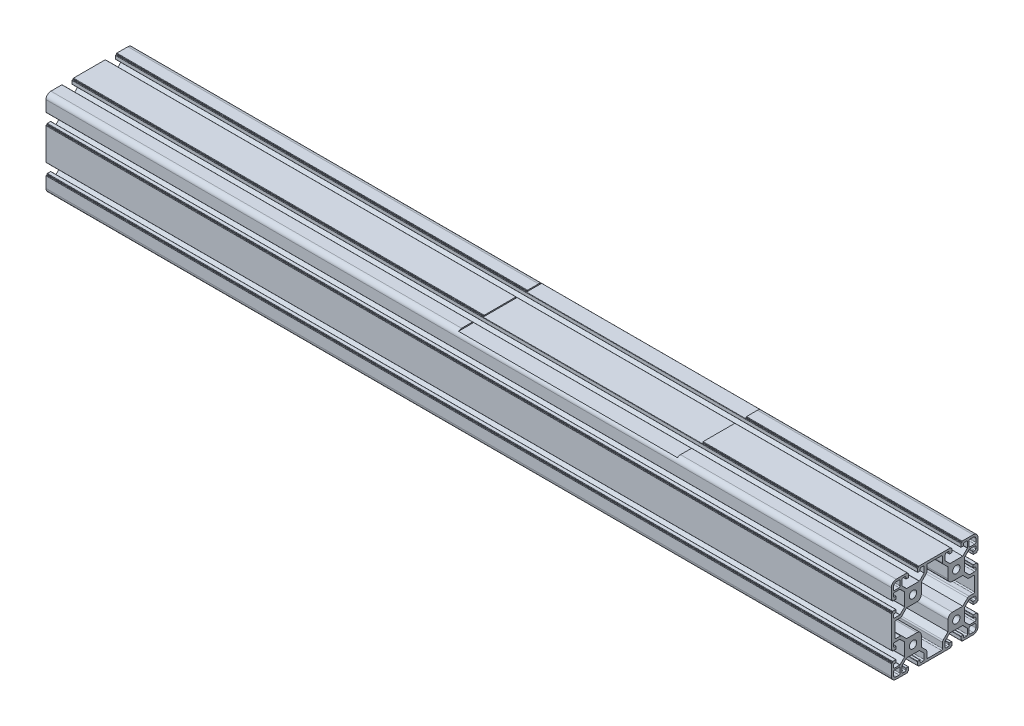
SolidWorks part; units mm, degrees
ref_plane "前视基准面" through (0, 0, 0) normal (0, 0, 1) x (1, 0, 0)
ref_plane "上视基准面" through (0, 0, 0) normal (0, 1, 0) x (1, 0, 0)
ref_plane "右视基准面" through (0, 0, 0) normal (1, 0, 0) x (0, 0, -1)
sketch "草图1" plane through (0, 0, 0) normal (0, 0, 1) x (1, 0, 0)
  line L0 (0, 0) -> (780, 0)
  dimension "D1" = 780
other "铝型材（gb t5237-2004） 8080(1)" corner treatment miter
ref_plane "基准面1" through (0, 0, 0) normal (1, 0, 0) x (0, 1, 0)
sketch "草图19" plane through (0, 0, 0) normal (1, 0, 0) x (0, 1, 0)
  line L2 (-25.808, -27.7) -> (-14.192, -27.7)
  line L3 (-14.9, 39.7) -> (-14.9, 39.2)
  line L4 (-10.75, -38) -> (-12.4, -38)
  line L5 (-15.9, -35.8) -> (-15.9, -38.7)
  line L6 (-15.6, -39) -> (-15.1, -39)
  line L7 (10.75, 38) -> (12.4, 38)
  line L8 (14.9, -39.7) -> (14.9, -39.2)
  line L9 (25.808, 27.7) -> (14.192, 27.7)
  line L10 (30.1621, 31.9299) -> (26.0201, 27.7879)
  line L11 (15.6, -35.5) -> (13.7, -35.5)
  line L12 (27.6, 38) -> (29.25, 38)
  line L13 (26.6, 35.8) -> (26.6, 37)
  line L14 (9.75, -37) -> (9.75, -32.142)
  line L15 (24.1, 38.7) -> (24.1, 35.8)
  line L16 (9.8379, -31.9299) -> (13.9799, -27.7879)
  line L17 (24.9, 39) -> (24.4, 39)
  line L18 (26.0201, -27.7879) -> (30.1621, -31.9299)
  line L19 (30.25, -32.142) -> (30.25, -37)
  line L20 (31.8107, 7.25) -> (36.8, 7.25)
  line L21 (-37.8, -6.25) -> (-37.8, 6.25)
  line L25 (-35.5, 13.7) -> (-35.5, 15.6)
  line L26 (-35.8, 15.9) -> (-38.7, 15.9)
  line L27 (-37, 13.4) -> (-35.8, 13.4)
  line L28 (-39, 15.6) -> (-39, 15.1)
  line L29 (-38, 10.75) -> (-38, 12.4)
  line L30 (-39.2, 14.9) -> (-39.7, 14.9)
  line L31 (-32.0178, 9.75) -> (-37, 9.75)
  line L32 (-27.7879, 13.9799) -> (-32.0178, 9.75)
  line L33 (-40, 14.6) -> (-40, -14.6)
  line L34 (-27.7, 25.808) -> (-27.7, 14.192)
  line L35 (-39.7, -14.9) -> (-39.2, -14.9)
  line L36 (-31.9299, 30.1621) -> (-27.7879, 26.0201)
  line L37 (-39, -15.1) -> (-39, -15.6)
  line L38 (-37, 30.25) -> (-32.142, 30.25)
  line L39 (-38.7, -15.9) -> (-35.8, -15.9)
  line L40 (-38, 27.6) -> (-38, 29.25)
  line L41 (-35.5, -15.6) -> (-35.5, -13.7)
  line L42 (-35.8, 26.6) -> (-37, 26.6)
  line L43 (-35.8, -13.4) -> (-37, -13.4)
  line L44 (-35.5, 24.4) -> (-35.5, 26.3)
  line L45 (-38, -12.4) -> (-38, -10.75)
  line L46 (-38.7, 24.1) -> (-35.8, 24.1)
  line L47 (-37, -9.75) -> (-32.0178, -9.75)
  line L48 (-32.0178, -9.75) -> (-27.7879, -13.9799)
  line L49 (-39, 24.9) -> (-39, 24.4)
  line L50 (-27.7, -14.192) -> (-27.7, -25.808)
  line L51 (-39.7, 25.1) -> (-39.2, 25.1)
  line L52 (-27.7879, -26.0201) -> (-31.9299, -30.1621)
  line L53 (-40, 35.5) -> (-40, 25.4)
  line L54 (-32.142, -30.25) -> (-37, -30.25)
  line L55 (-25.4, 40) -> (-35.5, 40)
  line L56 (-38, -29.25) -> (-38, -27.6)
  line L57 (-25.1, 39.2) -> (-25.1, 39.7)
  line L58 (-37, -26.6) -> (-35.8, -26.6)
  line L59 (-24.4, 39) -> (-24.9, 39)
  line L60 (-35.5, -26.3) -> (-35.5, -24.4)
  line L61 (-24.1, 35.8) -> (-24.1, 38.7)
  line L62 (-35.8, -24.1) -> (-38.7, -24.1)
  line L63 (-26.3, 35.5) -> (-24.4, 35.5)
  line L64 (-39, -24.4) -> (-39, -24.9)
  line L65 (-26.6, 37) -> (-26.6, 35.8)
  line L66 (-39.2, -25.1) -> (-39.7, -25.1)
  line L67 (-29.25, 38) -> (-27.6, 38)
  line L68 (-40, -25.4) -> (-40, -35.5)
  line L69 (-30.25, 32.142) -> (-30.25, 37)
  line L70 (-35.5, -40) -> (-25.4, -40)
  line L71 (-26.0201, 27.7879) -> (-30.1621, 31.9299)
  line L72 (-25.1, -39.7) -> (-25.1, -39.2)
  line L73 (-14.192, 27.7) -> (-25.808, 27.7)
  line L74 (-24.9, -39) -> (-24.4, -39)
  line L75 (-9.8379, 31.9299) -> (-13.9799, 27.7879)
  line L76 (-24.1, -38.7) -> (-24.1, -35.8)
  line L77 (-9.75, 37) -> (-9.75, 32.142)
  line L78 (-24.4, -35.5) -> (-26.3, -35.5)
  line L79 (-12.4, 38) -> (-10.75, 38)
  line L80 (-26.6, -35.8) -> (-26.6, -37)
  line L81 (-13.4, 35.8) -> (-13.4, 37)
  line L82 (-27.6, -38) -> (-29.25, -38)
  line L83 (-15.6, 35.5) -> (-13.7, 35.5)
  line L84 (-30.25, -37) -> (-30.25, -32.142)
  line L85 (-15.9, 38.7) -> (-15.9, 35.8)
  line L86 (-30.1621, -31.9299) -> (-26.0201, -27.7879)
  line L87 (-15.1, 39) -> (-15.6, 39)
  line L88 (-13.9799, -27.7879) -> (-9.8379, -31.9299)
  line L89 (14.6, 40) -> (-14.6, 40)
  line L90 (-9.75, -32.142) -> (-9.75, -37)
  line L91 (14.9, 39.2) -> (14.9, 39.7)
  line L92 (15.6, 39) -> (15.1, 39)
  line L93 (-13.4, -37) -> (-13.4, -35.8)
  line L94 (15.9, 35.8) -> (15.9, 38.7)
  line L95 (-13.7, -35.5) -> (-15.6, -35.5)
  line L96 (13.7, 35.5) -> (15.6, 35.5)
  line L97 (13.4, 37) -> (13.4, 35.8)
  line L98 (-14.9, -39.2) -> (-14.9, -39.7)
  line L99 (9.75, 32.142) -> (9.75, 37)
  line L100 (-14.6, -40) -> (14.6, -40)
  line L101 (13.9799, 27.7879) -> (9.8379, 31.9299)
  line L102 (15.1, -39) -> (15.6, -39)
  line L103 (15.9, -38.7) -> (15.9, -35.8)
  line L104 (30.25, 37) -> (30.25, 32.142)
  line L105 (13.4, -35.8) -> (13.4, -37)
  line L106 (12.4, -38) -> (10.75, -38)
  line L107 (24.4, 35.5) -> (26.3, 35.5)
  line L108 (14.192, -27.7) -> (25.808, -27.7)
  line L109 (25.1, 39.7) -> (25.1, 39.2)
  line L110 (35.5, 40) -> (25.4, 40)
  line L111 (40, 25.4) -> (40, 35.5)
  line L112 (29.25, -38) -> (27.6, -38)
  line L113 (39.2, 25.1) -> (39.7, 25.1)
  line L114 (26.6, -37) -> (26.6, -35.8)
  line L115 (39, 24.4) -> (39, 24.9)
  line L116 (26.3, -35.5) -> (24.4, -35.5)
  line L117 (35.8, 24.1) -> (38.7, 24.1)
  line L118 (24.1, -35.8) -> (24.1, -38.7)
  line L119 (35.5, 26.3) -> (35.5, 24.4)
  line L120 (24.4, -39) -> (24.9, -39)
  line L121 (37, 26.6) -> (35.8, 26.6)
  line L122 (25.1, -39.2) -> (25.1, -39.7)
  line L123 (38, 29.25) -> (38, 27.6)
  line L124 (25.4, -40) -> (35.5, -40)
  line L125 (32.142, 30.25) -> (37, 30.25)
  line L126 (40, -35.5) -> (40, -25.4)
  line L127 (27.7879, 26.0201) -> (31.9299, 30.1621)
  line L128 (39.7, -25.1) -> (39.2, -25.1)
  line L129 (27.7, 14.192) -> (27.7, 25.808)
  line L130 (39, -24.9) -> (39, -24.4)
  line L131 (32.0178, 9.75) -> (27.7879, 13.9799)
  line L132 (37, 9.75) -> (32.0178, 9.75)
  line L133 (38.7, -24.1) -> (35.8, -24.1)
  line L134 (38, 12.4) -> (38, 10.75)
  line L135 (35.5, -24.4) -> (35.5, -26.3)
  line L136 (35.8, 13.4) -> (37, 13.4)
  line L137 (35.8, -26.6) -> (37, -26.6)
  line L138 (35.5, 15.6) -> (35.5, 13.7)
  line L139 (38, -27.6) -> (38, -29.25)
  line L140 (38.7, 15.9) -> (35.8, 15.9)
  line L141 (37, -30.25) -> (32.142, -30.25)
  line L142 (39, 15.1) -> (39, 15.6)
  line L143 (31.9299, -30.1621) -> (27.7, -25.9322)
  line L144 (27.7, -25.9322) -> (27.7, -14.0678)
  line L145 (39.7, 14.9) -> (39.2, 14.9)
  line L146 (27.7, -14.0678) -> (32.0178, -9.75)
  line L147 (32.0178, -9.75) -> (37, -9.75)
  line L148 (40, -14.6) -> (40, 14.6)
  line L149 (38, -10.75) -> (38, -12.4)
  line L150 (39.2, -14.9) -> (39.7, -14.9)
  line L151 (37, -13.4) -> (35.8, -13.4)
  line L152 (39, -15.6) -> (39, -15.1)
  line L153 (35.5, -13.7) -> (35.5, -15.6)
  line L154 (35.8, -15.9) -> (38.7, -15.9)
  line L155 (-6.25, 36.8) -> (6.25, 36.8)
  line L156 (7.25, 35.8) -> (7.25, 31.8107)
  line L157 (-7.25, 31.8107) -> (-7.25, 35.8)
  line L158 (7.8358, 30.3964) -> (12.3, 25.9322)
  line L159 (-12.3, 25.9322) -> (-7.8358, 30.3964)
  line L160 (12.3, 25.9322) -> (12.3, 16.3)
  line L161 (-12.3, 16.3) -> (-12.3, 25.9322)
  line L162 (16.3, 12.3) -> (25.9322, 12.3)
  line L163 (-25.9322, 12.3) -> (-16.3, 12.3)
  line L164 (25.9322, 12.3) -> (30.3964, 7.8358)
  line L165 (-30.3964, 7.8358) -> (-25.9322, 12.3)
  line L166 (-36.8, 7.25) -> (-31.8107, 7.25)
  line L167 (37.8, 6.25) -> (37.8, -6.25)
  line L168 (36.8, -7.25) -> (31.8107, -7.25)
  line L169 (-31.8107, -7.25) -> (-36.8, -7.25)
  line L170 (30.3964, -7.8358) -> (25.9322, -12.3)
  line L171 (-25.9322, -12.3) -> (-30.3964, -7.8358)
  line L172 (25.9322, -12.3) -> (16.3, -12.3)
  line L173 (-16.3, -12.3) -> (-25.9322, -12.3)
  line L174 (12.3, -16.3) -> (12.3, -25.9322)
  line L175 (-12.3, -25.9322) -> (-12.3, -16.3)
  line L176 (12.3, -25.9322) -> (7.8358, -30.3964)
  line L177 (-7.8358, -30.3964) -> (-12.3, -25.9322)
  line L178 (7.25, -31.8107) -> (7.25, -35.8)
  line L179 (-7.25, -35.8) -> (-7.25, -31.8107)
  line L180 (6.25, -36.8) -> (-6.25, -36.8)
  line L181 (38, 35.5) -> (38, 32.75)
  line L182 (32.75, 38) -> (35.5, 38)
  line L183 (37, 31.75) -> (32.75, 31.75)
  line L184 (31.75, 32.75) -> (31.75, 37)
  line L185 (-35.5, 38) -> (-32.75, 38)
  line L186 (-38, 32.75) -> (-38, 35.5)
  line L187 (-31.75, 37) -> (-31.75, 32.75)
  line L188 (-32.75, 31.75) -> (-37, 31.75)
  line L189 (-38, -35.5) -> (-38, -32.75)
  line L190 (-32.75, -38) -> (-35.5, -38)
  line L191 (-37, -31.75) -> (-32.75, -31.75)
  line L192 (-31.75, -32.75) -> (-31.75, -37)
  line L193 (35.5, -38) -> (32.75, -38)
  line L194 (38, -32.75) -> (38, -35.5)
  line L195 (31.75, -37) -> (31.75, -32.75)
  line L196 (32.75, -31.75) -> (37, -31.75)
  arc A0 (-9.75, -32.142) -> (-9.8379, -31.9299) centre (-10.05, -32.142) ccw
  arc A1 (14.9, 39.7) -> (14.6, 40) centre (14.6, 39.7) ccw
  arc A2 (-15.6, -35.5) -> (-15.9, -35.8) centre (-15.6, -35.8) ccw
  arc A3 (13.4, 35.8) -> (13.7, 35.5) centre (13.7, 35.8) ccw
  arc A4 (-14.9, -39.2) -> (-15.1, -39) centre (-15.1, -39.2) ccw
  arc A5 (9.75, 32.142) -> (9.8379, 31.9299) centre (10.05, 32.142) ccw
  arc A6 (15.6, -39) -> (15.9, -38.7) centre (15.6, -38.7) ccw
  arc A7 (30.1621, 31.9299) -> (30.25, 32.142) centre (29.95, 32.142) ccw
  arc A8 (30.25, 37) -> (29.25, 38) centre (29.25, 37) ccw
  arc A9 (12.4, -38) -> (13.4, -37) centre (12.4, -37) ccw
  arc A10 (26.3, 35.5) -> (26.6, 35.8) centre (26.3, 35.8) ccw
  arc A11 (24.1, 35.8) -> (24.4, 35.5) centre (24.4, 35.8) ccw
  arc A12 (14.192, -27.7) -> (13.9799, -27.7879) centre (14.192, -28) ccw
  arc A13 (24.9, 39) -> (25.1, 39.2) centre (24.9, 39.2) ccw
  arc A14 (26.0201, -27.7879) -> (25.808, -27.7) centre (25.808, -28) ccw
  arc A15 (25.4, 40) -> (25.1, 39.7) centre (25.4, 39.7) ccw
  arc A16 (-31.8107, 7.25) -> (-30.3964, 7.8358) centre (-31.8107, 9.25) ccw
  arc A17 (36.8, -7.25) -> (37.8, -6.25) centre (36.8, -6.25) ccw
  arc A18 (-35.5, 15.6) -> (-35.8, 15.9) centre (-35.8, 15.6) ccw
  arc A19 (-35.8, 13.4) -> (-35.5, 13.7) centre (-35.8, 13.7) ccw
  arc A20 (-38.7, 15.9) -> (-39, 15.6) centre (-38.7, 15.6) ccw
  arc A21 (-37, 13.4) -> (-38, 12.4) centre (-37, 12.4) ccw
  arc A22 (-39.2, 14.9) -> (-39, 15.1) centre (-39.2, 15.1) ccw
  arc A23 (-38, 10.75) -> (-37, 9.75) centre (-37, 10.75) ccw
  arc A24 (-39.7, 14.9) -> (-40, 14.6) centre (-39.7, 14.6) ccw
  arc A25 (-27.7879, 13.9799) -> (-27.7, 14.192) centre (-28, 14.192) ccw
  arc A26 (-40, -14.6) -> (-39.7, -14.9) centre (-39.7, -14.6) ccw
  arc A27 (-27.7, 25.808) -> (-27.7879, 26.0201) centre (-28, 25.808) ccw
  arc A28 (-39, -15.1) -> (-39.2, -14.9) centre (-39.2, -15.1) ccw
  arc A29 (-31.9299, 30.1621) -> (-32.142, 30.25) centre (-32.142, 29.95) ccw
  arc A30 (-39, -15.6) -> (-38.7, -15.9) centre (-38.7, -15.6) ccw
  arc A31 (-37, 30.25) -> (-38, 29.25) centre (-37, 29.25) ccw
  arc A32 (-35.8, -15.9) -> (-35.5, -15.6) centre (-35.8, -15.6) ccw
  arc A33 (-38, 27.6) -> (-37, 26.6) centre (-37, 27.6) ccw
  arc A34 (-35.5, -13.7) -> (-35.8, -13.4) centre (-35.8, -13.7) ccw
  arc A35 (-35.5, 26.3) -> (-35.8, 26.6) centre (-35.8, 26.3) ccw
  arc A36 (-38, -12.4) -> (-37, -13.4) centre (-37, -12.4) ccw
  arc A37 (-35.8, 24.1) -> (-35.5, 24.4) centre (-35.8, 24.4) ccw
  arc A38 (-37, -9.75) -> (-38, -10.75) centre (-37, -10.75) ccw
  arc A39 (-39, 24.4) -> (-38.7, 24.1) centre (-38.7, 24.4) ccw
  arc A40 (-27.7, -14.192) -> (-27.7879, -13.9799) centre (-28, -14.192) ccw
  arc A41 (-39, 24.9) -> (-39.2, 25.1) centre (-39.2, 24.9) ccw
  arc A42 (-27.7879, -26.0201) -> (-27.7, -25.808) centre (-28, -25.808) ccw
  arc A43 (-40, 25.4) -> (-39.7, 25.1) centre (-39.7, 25.4) ccw
  arc A44 (-32.142, -30.25) -> (-31.9299, -30.1621) centre (-32.142, -29.95) ccw
  arc A45 (-35.5, 40) -> (-40, 35.5) centre (-35.5, 35.5) ccw
  arc A46 (-38, -29.25) -> (-37, -30.25) centre (-37, -29.25) ccw
  arc A47 (-25.1, 39.7) -> (-25.4, 40) centre (-25.4, 39.7) ccw
  arc A48 (-37, -26.6) -> (-38, -27.6) centre (-37, -27.6) ccw
  arc A49 (-25.1, 39.2) -> (-24.9, 39) centre (-24.9, 39.2) ccw
  arc A50 (-35.8, -26.6) -> (-35.5, -26.3) centre (-35.8, -26.3) ccw
  arc A51 (-24.1, 38.7) -> (-24.4, 39) centre (-24.4, 38.7) ccw
  arc A52 (-35.5, -24.4) -> (-35.8, -24.1) centre (-35.8, -24.4) ccw
  arc A53 (-24.4, 35.5) -> (-24.1, 35.8) centre (-24.4, 35.8) ccw
  arc A54 (-38.7, -24.1) -> (-39, -24.4) centre (-38.7, -24.4) ccw
  arc A55 (-26.6, 35.8) -> (-26.3, 35.5) centre (-26.3, 35.8) ccw
  arc A56 (-39.2, -25.1) -> (-39, -24.9) centre (-39.2, -24.9) ccw
  arc A57 (-26.6, 37) -> (-27.6, 38) centre (-27.6, 37) ccw
  arc A58 (-39.7, -25.1) -> (-40, -25.4) centre (-39.7, -25.4) ccw
  arc A59 (-29.25, 38) -> (-30.25, 37) centre (-29.25, 37) ccw
  arc A60 (-40, -35.5) -> (-35.5, -40) centre (-35.5, -35.5) ccw
  arc A61 (-30.25, 32.142) -> (-30.1621, 31.9299) centre (-29.95, 32.142) ccw
  arc A62 (-25.4, -40) -> (-25.1, -39.7) centre (-25.4, -39.7) ccw
  arc A63 (-26.0201, 27.7879) -> (-25.808, 27.7) centre (-25.808, 28) ccw
  arc A64 (-24.9, -39) -> (-25.1, -39.2) centre (-24.9, -39.2) ccw
  arc A65 (-14.192, 27.7) -> (-13.9799, 27.7879) centre (-14.192, 28) ccw
  arc A66 (-24.4, -39) -> (-24.1, -38.7) centre (-24.4, -38.7) ccw
  arc A67 (-9.8379, 31.9299) -> (-9.75, 32.142) centre (-10.05, 32.142) ccw
  arc A68 (-24.1, -35.8) -> (-24.4, -35.5) centre (-24.4, -35.8) ccw
  arc A69 (-9.75, 37) -> (-10.75, 38) centre (-10.75, 37) ccw
  arc A70 (-26.3, -35.5) -> (-26.6, -35.8) centre (-26.3, -35.8) ccw
  arc A71 (-12.4, 38) -> (-13.4, 37) centre (-12.4, 37) ccw
  arc A72 (-27.6, -38) -> (-26.6, -37) centre (-27.6, -37) ccw
  arc A73 (-13.7, 35.5) -> (-13.4, 35.8) centre (-13.7, 35.8) ccw
  arc A74 (-30.25, -37) -> (-29.25, -38) centre (-29.25, -37) ccw
  arc A75 (-15.9, 35.8) -> (-15.6, 35.5) centre (-15.6, 35.8) ccw
  arc A76 (-30.1621, -31.9299) -> (-30.25, -32.142) centre (-29.95, -32.142) ccw
  arc A77 (-15.6, 39) -> (-15.9, 38.7) centre (-15.6, 38.7) ccw
  arc A78 (-25.808, -27.7) -> (-26.0201, -27.7879) centre (-25.808, -28) ccw
  arc A79 (-15.1, 39) -> (-14.9, 39.2) centre (-15.1, 39.2) ccw
  arc A80 (-13.9799, -27.7879) -> (-14.192, -27.7) centre (-14.192, -28) ccw
  arc A81 (-14.6, 40) -> (-14.9, 39.7) centre (-14.6, 39.7) ccw
  arc A82 (-10.75, -38) -> (-9.75, -37) centre (-10.75, -37) ccw
  arc A83 (14.9, 39.2) -> (15.1, 39) centre (15.1, 39.2) ccw
  arc A84 (-13.4, -37) -> (-12.4, -38) centre (-12.4, -37) ccw
  arc A85 (15.9, 38.7) -> (15.6, 39) centre (15.6, 38.7) ccw
  arc A86 (-13.4, -35.8) -> (-13.7, -35.5) centre (-13.7, -35.8) ccw
  arc A87 (15.6, 35.5) -> (15.9, 35.8) centre (15.6, 35.8) ccw
  arc A88 (-15.9, -38.7) -> (-15.6, -39) centre (-15.6, -38.7) ccw
  arc A89 (13.4, 37) -> (12.4, 38) centre (12.4, 37) ccw
  arc A90 (10.75, 38) -> (9.75, 37) centre (10.75, 37) ccw
  arc A91 (-14.9, -39.7) -> (-14.6, -40) centre (-14.6, -39.7) ccw
  arc A92 (14.6, -40) -> (14.9, -39.7) centre (14.6, -39.7) ccw
  arc A93 (13.9799, 27.7879) -> (14.192, 27.7) centre (14.192, 28) ccw
  arc A94 (15.1, -39) -> (14.9, -39.2) centre (15.1, -39.2) ccw
  arc A95 (25.808, 27.7) -> (26.0201, 27.7879) centre (25.808, 28) ccw
  arc A96 (15.9, -35.8) -> (15.6, -35.5) centre (15.6, -35.8) ccw
  arc A97 (13.7, -35.5) -> (13.4, -35.8) centre (13.7, -35.8) ccw
  arc A98 (27.6, 38) -> (26.6, 37) centre (27.6, 37) ccw
  arc A99 (9.75, -37) -> (10.75, -38) centre (10.75, -37) ccw
  arc A100 (9.8379, -31.9299) -> (9.75, -32.142) centre (10.05, -32.142) ccw
  arc A101 (24.4, 39) -> (24.1, 38.7) centre (24.4, 38.7) ccw
  arc A102 (30.25, -32.142) -> (30.1621, -31.9299) centre (29.95, -32.142) ccw
  arc A103 (40, 35.5) -> (35.5, 40) centre (35.5, 35.5) ccw
  arc A104 (29.25, -38) -> (30.25, -37) centre (29.25, -37) ccw
  arc A105 (39.7, 25.1) -> (40, 25.4) centre (39.7, 25.4) ccw
  arc A106 (26.6, -37) -> (27.6, -38) centre (27.6, -37) ccw
  arc A107 (39.2, 25.1) -> (39, 24.9) centre (39.2, 24.9) ccw
  arc A108 (26.6, -35.8) -> (26.3, -35.5) centre (26.3, -35.8) ccw
  arc A109 (38.7, 24.1) -> (39, 24.4) centre (38.7, 24.4) ccw
  arc A110 (24.4, -35.5) -> (24.1, -35.8) centre (24.4, -35.8) ccw
  arc A111 (35.5, 24.4) -> (35.8, 24.1) centre (35.8, 24.4) ccw
  arc A112 (24.1, -38.7) -> (24.4, -39) centre (24.4, -38.7) ccw
  arc A113 (35.8, 26.6) -> (35.5, 26.3) centre (35.8, 26.3) ccw
  arc A114 (25.1, -39.2) -> (24.9, -39) centre (24.9, -39.2) ccw
  arc A115 (37, 26.6) -> (38, 27.6) centre (37, 27.6) ccw
  arc A116 (25.1, -39.7) -> (25.4, -40) centre (25.4, -39.7) ccw
  arc A117 (38, 29.25) -> (37, 30.25) centre (37, 29.25) ccw
  arc A118 (35.5, -40) -> (40, -35.5) centre (35.5, -35.5) ccw
  arc A119 (32.142, 30.25) -> (31.9299, 30.1621) centre (32.142, 29.95) ccw
  arc A120 (40, -25.4) -> (39.7, -25.1) centre (39.7, -25.4) ccw
  arc A121 (27.7879, 26.0201) -> (27.7, 25.808) centre (28, 25.808) ccw
  arc A122 (39, -24.9) -> (39.2, -25.1) centre (39.2, -24.9) ccw
  arc A123 (27.7, 14.192) -> (27.7879, 13.9799) centre (28, 14.192) ccw
  arc A124 (39, -24.4) -> (38.7, -24.1) centre (38.7, -24.4) ccw
  arc A125 (37, 9.75) -> (38, 10.75) centre (37, 10.75) ccw
  arc A126 (35.8, -24.1) -> (35.5, -24.4) centre (35.8, -24.4) ccw
  arc A127 (38, 12.4) -> (37, 13.4) centre (37, 12.4) ccw
  arc A128 (35.5, -26.3) -> (35.8, -26.6) centre (35.8, -26.3) ccw
  arc A129 (35.5, 13.7) -> (35.8, 13.4) centre (35.8, 13.7) ccw
  arc A130 (38, -27.6) -> (37, -26.6) centre (37, -27.6) ccw
  arc A131 (35.8, 15.9) -> (35.5, 15.6) centre (35.8, 15.6) ccw
  arc A132 (37, -30.25) -> (38, -29.25) centre (37, -29.25) ccw
  arc A133 (39, 15.6) -> (38.7, 15.9) centre (38.7, 15.6) ccw
  arc A134 (31.9299, -30.1621) -> (32.142, -30.25) centre (32.142, -29.95) ccw
  arc A135 (39, 15.1) -> (39.2, 14.9) centre (39.2, 15.1) ccw
  arc A136 (40, 14.6) -> (39.7, 14.9) centre (39.7, 14.6) ccw
  arc A137 (38, -10.75) -> (37, -9.75) centre (37, -10.75) ccw
  arc A138 (39.7, -14.9) -> (40, -14.6) centre (39.7, -14.6) ccw
  arc A139 (37, -13.4) -> (38, -12.4) centre (37, -12.4) ccw
  arc A140 (39.2, -14.9) -> (39, -15.1) centre (39.2, -15.1) ccw
  arc A141 (35.8, -13.4) -> (35.5, -13.7) centre (35.8, -13.7) ccw
  arc A142 (38.7, -15.9) -> (39, -15.6) centre (38.7, -15.6) ccw
  arc A143 (35.5, -15.6) -> (35.8, -15.9) centre (35.8, -15.6) ccw
  arc A144 (7.25, 35.8) -> (6.25, 36.8) centre (6.25, 35.8) ccw
  arc A145 (-6.25, 36.8) -> (-7.25, 35.8) centre (-6.25, 35.8) ccw
  arc A146 (7.25, 31.8107) -> (7.8358, 30.3964) centre (9.25, 31.8107) ccw
  arc A147 (-7.8358, 30.3964) -> (-7.25, 31.8107) centre (-9.25, 31.8107) ccw
  arc A148 (12.3, 16.3) -> (16.3, 12.3) centre (16.3, 16.3) ccw
  arc A149 (-16.3, 12.3) -> (-12.3, 16.3) centre (-16.3, 16.3) ccw
  arc A150 (30.3964, 7.8358) -> (31.8107, 7.25) centre (31.8107, 9.25) ccw
  arc A151 (37.8, 6.25) -> (36.8, 7.25) centre (36.8, 6.25) ccw
  arc A152 (-36.8, 7.25) -> (-37.8, 6.25) centre (-36.8, 6.25) ccw
  arc A153 (-37.8, -6.25) -> (-36.8, -7.25) centre (-36.8, -6.25) ccw
  arc A154 (31.8107, -7.25) -> (30.3964, -7.8358) centre (31.8107, -9.25) ccw
  arc A155 (-30.3964, -7.8358) -> (-31.8107, -7.25) centre (-31.8107, -9.25) ccw
  arc A156 (16.3, -12.3) -> (12.3, -16.3) centre (16.3, -16.3) ccw
  arc A157 (-12.3, -16.3) -> (-16.3, -12.3) centre (-16.3, -16.3) ccw
  arc A158 (7.8358, -30.3964) -> (7.25, -31.8107) centre (9.25, -31.8107) ccw
  arc A159 (-7.25, -31.8107) -> (-7.8358, -30.3964) centre (-9.25, -31.8107) ccw
  arc A160 (6.25, -36.8) -> (7.25, -35.8) centre (6.25, -35.8) ccw
  arc A161 (-7.25, -35.8) -> (-6.25, -36.8) centre (-6.25, -35.8) ccw
  circle A162 centre (20, -20) radius 3.4
  circle A163 centre (-20, -20) radius 3.4
  circle A164 centre (-20, 20) radius 3.4
  arc A165 (38, 35.5) -> (35.5, 38) centre (35.5, 35.5) ccw
  arc A166 (37, 31.75) -> (38, 32.75) centre (37, 32.75) ccw
  arc A167 (32.75, 38) -> (31.75, 37) centre (32.75, 37) ccw
  arc A168 (31.75, 32.75) -> (32.75, 31.75) centre (32.75, 32.75) ccw
  circle A169 centre (20, 20) radius 3.4
  arc A170 (-35.5, 38) -> (-38, 35.5) centre (-35.5, 35.5) ccw
  arc A171 (-31.75, 37) -> (-32.75, 38) centre (-32.75, 37) ccw
  arc A172 (-38, 32.75) -> (-37, 31.75) centre (-37, 32.75) ccw
  arc A173 (-32.75, 31.75) -> (-31.75, 32.75) centre (-32.75, 32.75) ccw
  arc A174 (-38, -35.5) -> (-35.5, -38) centre (-35.5, -35.5) ccw
  arc A175 (-37, -31.75) -> (-38, -32.75) centre (-37, -32.75) ccw
  arc A176 (-32.75, -38) -> (-31.75, -37) centre (-32.75, -37) ccw
  arc A177 (-31.75, -32.75) -> (-32.75, -31.75) centre (-32.75, -32.75) ccw
  arc A178 (35.5, -38) -> (38, -35.5) centre (35.5, -35.5) ccw
  arc A179 (31.75, -37) -> (32.75, -38) centre (32.75, -37) ccw
  arc A180 (38, -32.75) -> (37, -31.75) centre (37, -32.75) ccw
  arc A181 (32.75, -31.75) -> (31.75, -32.75) centre (32.75, -32.75) ccw
  point P0 (0, 0)
sketch "草图20" plane through (0, 40, 0) normal (0, 1, 0) x (1, 0, 0)
  line L0 (780, 0) -> (480, 0) construction
  line L1 (780, 14.6) -> (780, -14.6) construction
  line L2 (780, -40) -> (0, -40) construction
  line L3 (379, 40) -> (581, 40)
  line L4 (379, 40) -> (379, -40)
  line L5 (379, -40) -> (581, -40)
  line L6 (581, 40) -> (581, -40)
  line L7 (379, 40) -> (581, -40) construction
  line L8 (379, -40) -> (581, 40) construction
  dimension "D1" = 300
  dimension "D2" = 202
extrude "切除-拉伸1" cut sketch "草图20" against normal blind 1
sketch "草图21" plane through (0, -40, 0) normal (0, -1, 0) x (1, 0, 0)
  circle A0 centre (323, 0) radius 12.5
  circle A1 centre (222.9804, 0.6707) radius 12.5
extrude "切除-拉伸2" cut sketch "草图21" against normal blind 35
sketch "草图22" plane through (0, -40, 0) normal (0, -1, 0) x (1, 0, 0)
  line L0 (780, 0) -> (510, 0) construction
  line L1 (780, 14.6) -> (780, -14.6) construction
  line L2 (460, 0) -> (560, 0) construction
  line L3 (460, 12.5) -> (560, 12.5)
  line L4 (460, -12.5) -> (560, -12.5)
  arc A0 (460, 12.5) -> (460, -12.5) centre (460, 0) ccw
  arc A1 (560, -12.5) -> (560, 12.5) centre (560, 0) ccw
  point P5 (510, 0)
  dimension "D1" = 270
  dimension "D2" = 25
  dimension "D3" = 100
extrude "切除-拉伸3" cut sketch "草图22" against normal blind 30
